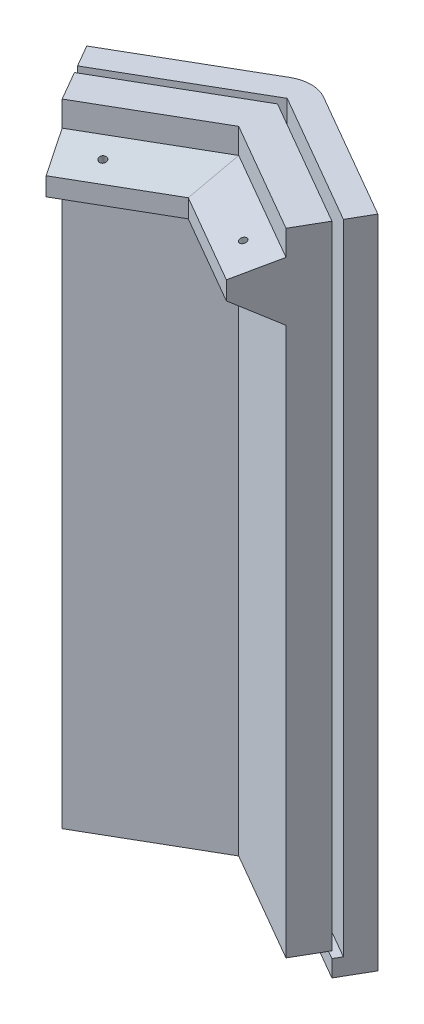
SolidWorks part; units mm, degrees
ref_plane "Front Plane" through (0, 0, 0) normal (0, 0, 1) x (1, 0, 0)
ref_plane "Top Plane" through (0, 0, 0) normal (0, 1, 0) x (1, 0, 0)
ref_plane "Right Plane" through (0, 0, 0) normal (1, 0, 0) x (0, 0, -1)
sketch "Sketch1" plane through (0, 0, 0) normal (0, 1, 0) x (1, 0, 0)
  line L0 (0, -153.0167) -> (0, 58.3538) construction
  line L1 (97.0301, 0) -> (-101.5537, 0) construction
  line L2 (-10, -5.7735) -> (-86.6025, -50)
  line L3 (10, -5.7735) -> (86.6025, -50)
  line L4 (0, -46.188) -> (66.6025, -84.641)
  line L5 (0, -46.188) -> (-66.6025, -84.641)
  line L6 (86.6025, -50) -> (66.6025, -84.641) construction
  line L7 (-86.6025, -50) -> (-66.6025, -84.641) construction
  line L8 (86.6025, -50) -> (79.1025, -62.9904)
  line L9 (79.1025, -62.9904) -> (53.1218, -47.9904)
  line L10 (53.1218, -47.9904) -> (50.6218, -52.3205)
  line L11 (50.6218, -52.3205) -> (76.6025, -67.3205)
  line L12 (76.6025, -67.3205) -> (66.6025, -84.641)
  line L13 (-86.6025, -50) -> (-79.1025, -62.9904)
  line L14 (-79.1025, -62.9904) -> (-53.1218, -47.9904)
  line L15 (-53.1218, -47.9904) -> (-50.6218, -52.3205)
  line L16 (-50.6218, -52.3205) -> (-76.6025, -67.3205)
  line L17 (-76.6025, -67.3205) -> (-66.6025, -84.641)
  circle A0 centre (0, -32) radius 20.5 construction
  arc A2 (-10, -5.7735) -> (10, -5.7735) centre (0, -23.094) cw
  point P24 (0, -46.188)
  point P27 (0, 0)
  dimension "D9" = 41
  dimension "D10" = 20
  dimension "D1" = 30
  dimension "D2" = 30
  dimension "D3" = 40
  dimension "D4" = 90
  dimension "D5" = 90
  dimension "D6" = 100
  dimension "D7" = 5
  dimension "D8" = 30
  dimension "D11" = 32
  dimension "D12" = 15
extrude "Boss-Extrude1" add sketch "Sketch1" along normal blind 390
sketch "Sketch18" plane through (0, 0, 0) normal (0, -1, 0) x (1, 0, 0)
  line L3 (-66.6025, 84.641) -> (0, 46.188) construction
  line L6 (-76.6025, 67.3205) -> (0, 23.094)
  line L7 (0, 23.094) -> (76.6025, 67.3205)
  line L8 (-76.6025, 67.3205) -> (0, 23.094)
  line L9 (0, 23.094) -> (76.6025, 67.3205)
  line L10 (0, 46.188) -> (66.6025, 84.641) construction
  line L11 (-66.6025, 84.641) -> (0, 46.188)
  line L12 (0, 46.188) -> (66.6025, 84.641)
  line L13 (76.6025, 67.3205) -> (66.6025, 84.641)
  line L15 (-76.6025, 67.3205) -> (-66.6025, 84.641)
  dimension "D1" = 20
extrude "Cut-Extrude2" cut sketch "Sketch18" against normal blind 14
sketch "Sketch19" plane through (0, 390, 0) normal (0, 1, 0) x (1, 0, 0)
  line L0 (76.6025, -67.3205) -> (50.6218, -52.3205) construction
  line L2 (76.6025, -67.3205) -> (0, -23.094)
  line L3 (79.1025, -62.9904) -> (76.6025, -67.3205)
  line L4 (53.1218, -47.9904) -> (79.1025, -62.9904) construction
  line L5 (0, -17.3205) -> (79.1025, -62.9904)
  line L6 (-79.1025, -62.9904) -> (-53.1218, -47.9904) construction
  line L7 (-79.1025, -62.9904) -> (0, -17.3205)
  line L8 (-50.6218, -52.3205) -> (-76.6025, -67.3205) construction
  line L9 (0, -23.094) -> (-76.6025, -67.3205)
  line L10 (-79.1025, -62.9904) -> (-76.6025, -67.3205)
extrude "Cut-Extrude3" cut sketch "Sketch19" against normal blind 50
sketch "Sketch20" plane through (0, 0, 0) normal (0, -1, 0) x (1, 0, 0)
  line L0 (76.6025, 67.3205) -> (50.6218, 52.3205) construction
  line L1 (53.1218, 47.9904) -> (79.1025, 62.9904) construction
  line L2 (50.6218, 52.3205) -> (53.1218, 47.9904) construction
  line L3 (-50.6218, 52.3205) -> (-76.6025, 67.3205) construction
  line L4 (-53.1218, 47.9904) -> (-50.6218, 52.3205) construction
  line L5 (-79.1025, 62.9904) -> (-53.1218, 47.9904) construction
  line L6 (76.6025, 67.3205) -> (50.6218, 52.3205)
  line L7 (53.1218, 47.9904) -> (79.1025, 62.9904)
  line L8 (50.6218, 52.3205) -> (53.1218, 47.9904)
  line L9 (-50.6218, 52.3205) -> (-76.6025, 67.3205)
  line L10 (-53.1218, 47.9904) -> (-50.6218, 52.3205)
  line L11 (-79.1025, 62.9904) -> (-53.1218, 47.9904)
  line L12 (79.1025, 62.9904) -> (76.6025, 67.3205)
  line L13 (-79.1025, 62.9904) -> (-76.6025, 67.3205)
extrude "Boss-Extrude2" add sketch "Sketch20" against normal blind 10
sketch "Sketch21" plane through (0, 0, 0) normal (1, 0, 0) x (0, 0, -1)
  line L0 (-46.188, 390) -> (-46.188, 14) construction
  line L1 (-46.188, 390) -> (-46.188, 14) construction
  line L2 (-46.188, 375) -> (-76.188, 368.2062)
  line L3 (-76.188, 368.2062) -> (-76.188, 357.3205)
  line L4 (-76.188, 357.3205) -> (-46.188, 340)
  line L5 (-46.188, 340) -> (-46.188, 375)
  line L6 (-46.188, 375) -> (-172.9071, 375) construction
  dimension "D1" = 361
  dimension "D2" = 12.76
  dimension "D3" = 30
  dimension "D4" = 60
  dimension "D5" = 35
extrude "Boss-Extrude3" add sketch "Sketch21" along direction (0.866, 0, -0.5) on the side against the normal up to surface (61.906 mm away) up to face at (-80.7692, 133.3333, 60.1036)
extrude "Boss-Extrude4" add sketch "Sketch21<2>" along direction (0.866, 0, 0.5) on the side of the normal up to surface (61.906 mm away) up to face at (71.6025, 202, 75.9808)
sketch "Sketch21<2>" plane through (0, 0, 0) normal (1, 0, 0) x (0, 0, -1) same geometry as "Sketch21"
sketch "Sketch22" plane through (47.1721, 360.7893, 81.7045) normal (0.1265, 0.9675, 0.2191) x (0.992, -0.1234, -0.0279)
  line L0 (-47.5541, 37.778) -> (-47.5541, 7.0184) construction
  line L1 (-101.6004, -23.1702) -> (-114.696, 0.2747) construction
  line L2 (-47.5541, 37.778) -> (-47.5541, 7.0184) construction
  line L3 (-101.6004, -23.1702) -> (-114.696, 0.2747) construction
  line L4 (-108.1482, -11.4478) -> (-56.0716, 17.6406) construction
  circle A0 centre (-89.6398, -1.1095) radius 2.1
  dimension "D1" = 4.2
  dimension "D2" = 21.2
extrude "Cut-Extrude4" cut sketch "Sketch22" against normal blind 15
mirror "Mirror1" about plane through (0, 0, 0) normal (1, 0, 0) of "Cut-Extrude4"
sketch "Sketch23" plane through (0, 14, 0) normal (0, -1, 0) x (1, 0, 0)
  line L0 (-66.6025, 84.641) -> (-76.6025, 67.3205) construction
  line L1 (-66.6025, 84.641) -> (-76.6025, 67.3205) construction
  line L2 (-71.6025, 75.9808) -> (0, 34.641) construction
  line L3 (0, 0) -> (0, 34.641) construction
  circle A0 centre (-25.9808, 49.641) radius 3.1
  circle A1 centre (-51.9615, 64.641) radius 3.1
  dimension "D1" = 6.2
  dimension "D2" = 30
  dimension "D3" = 30
extrude "Cut-Extrude5" cut sketch "Sketch23" against normal blind 60
mirror "Mirror2" about plane through (0, 0, 0) normal (1, 0, 0) of "Cut-Extrude5"
